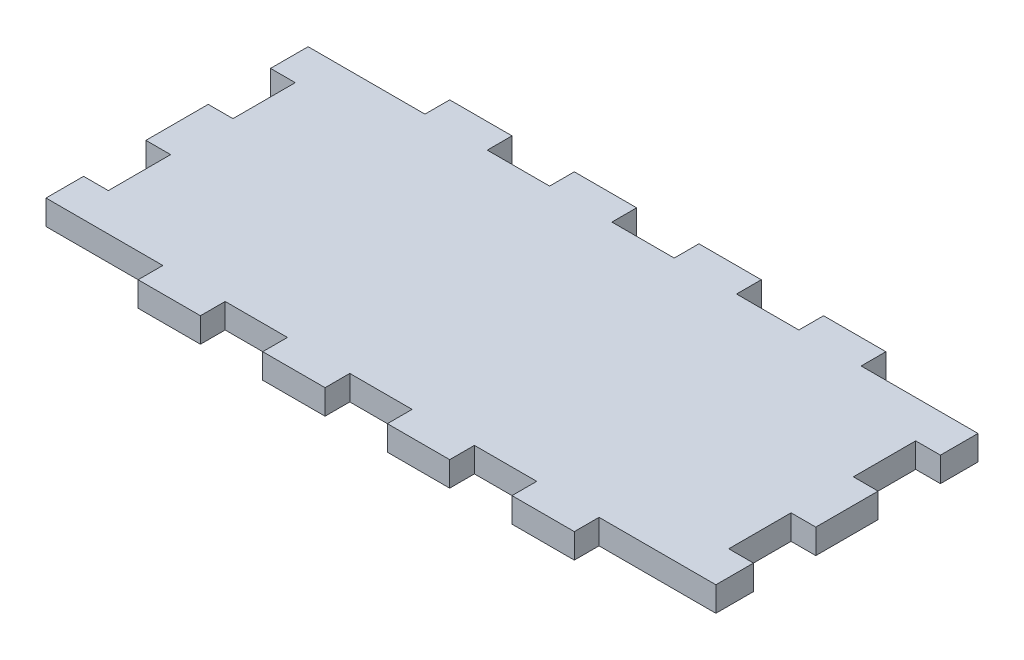
SolidWorks part; units mm, degrees
ref_plane "Front Plane" through (0, 0, 0) normal (0, 0, 1) x (1, 0, 0)
ref_plane "Top Plane" through (0, 0, 0) normal (0, 1, 0) x (1, 0, 0)
ref_plane "Right Plane" through (0, 0, 0) normal (1, 0, 0) x (0, 0, -1)
sketch "Sketch1" plane through (0, 0, 0) normal (0, 1, 0) x (1, 0, 0)
  line L1 (0, 0) -> (86, 0)
  line L2 (0, 0) -> (0, -40)
  line L3 (0, -40) -> (86, -40)
  line L4 (86, 0) -> (86, -40)
  dimension "D1" = 40
  dimension "D2" = 86
extrude "Boss-Extrude1" add sketch "Sketch1" along normal blind 3.175
sketch "Sketch2" plane through (0, 3.175, 0) normal (0, 1, 0) x (1, 0, 0)
  line L0 (43, 0) -> (43, -40) construction
  line L1 (86, 0) -> (0, 0) construction
  line L2 (0, -40) -> (86, -40) construction
  line L3 (0, -20) -> (86, -20) construction
  line L4 (0, 0) -> (0, -40) construction
  line L5 (86, -40) -> (86, 0) construction
  line L6 (15, 0) -> (15, -3.175)
  line L7 (39, 0) -> (47, 0)
  line L8 (0, -3.175) -> (15, -3.175)
  line L9 (39, -3.175) -> (47, -3.175)
  line L10 (47, 0) -> (47, -3.175)
  line L11 (55, 0) -> (63, 0)
  line L12 (55, 0) -> (55, -3.175)
  line L13 (55, -3.175) -> (63, -3.175)
  line L14 (63, 0) -> (63, -3.175)
  line L15 (86, 0) -> (71, 0)
  line L16 (86, 0) -> (86, -3.175)
  line L17 (86, -3.175) -> (71, -3.175)
  line L18 (71, 0) -> (71, -3.175)
  line L19 (0, 0) -> (0, -3.175)
  line L20 (0, 0) -> (15, 0)
  line L21 (23, 0) -> (23, -3.175)
  line L22 (31, -3.175) -> (23, -3.175)
  line L23 (31, 0) -> (31, -3.175)
  line L24 (31, 0) -> (23, 0)
  line L25 (39, 0) -> (39, -3.175)
  line L26 (39, -40) -> (39, -36.825)
  line L27 (31, -40) -> (23, -40)
  line L28 (31, -40) -> (31, -36.825)
  line L29 (31, -36.825) -> (23, -36.825)
  line L30 (23, -40) -> (23, -36.825)
  line L31 (0, -40) -> (15, -40)
  line L32 (0, -40) -> (0, -36.825)
  line L33 (71, -40) -> (71, -36.825)
  line L34 (86, -36.825) -> (71, -36.825)
  line L35 (86, -40) -> (86, -36.825)
  line L36 (86, -40) -> (71, -40)
  line L37 (63, -40) -> (63, -36.825)
  line L38 (55, -36.825) -> (63, -36.825)
  line L39 (55, -40) -> (55, -36.825)
  line L40 (55, -40) -> (63, -40)
  line L41 (47, -40) -> (47, -36.825)
  line L42 (39, -36.825) -> (47, -36.825)
  line L43 (0, -36.825) -> (15, -36.825)
  line L44 (39, -40) -> (47, -40)
  line L45 (15, -40) -> (15, -36.825)
  point P34 (43, -3.175)
  point P54 (43, -36.825)
  dimension "D1" = 4
  dimension "D2" = 3.175
  dimension "D3" = 3.175
  dimension "D4" = 8
  dimension "D5" = 8
  dimension "D6" = 3.175
  dimension "D7" = 8
extrude "Cut-Extrude1" cut sketch "Sketch2" against normal up to next
sketch "Sketch3" plane through (0, 3.175, 0) normal (0, 1, 0) x (1, 0, 0)
  line L0 (0, -20) -> (86, -20) construction
  line L1 (0, -3.175) -> (0, -36.825) construction
  line L2 (86, -36.825) -> (86, -3.175) construction
  line L3 (3.175, -24) -> (3.175, -32)
  line L4 (0, -16) -> (3.175, -16)
  line L5 (0, -16) -> (0, -8)
  line L6 (0, -8) -> (3.175, -8)
  line L7 (3.175, -16) -> (3.175, -8)
  line L8 (0, -32) -> (3.175, -32)
  line L9 (0, -24) -> (0, -32)
  line L10 (0, -24) -> (3.175, -24)
  line L11 (43, -3.175) -> (43, -36.825) construction
  line L12 (39, -3.175) -> (47, -3.175) construction
  line L13 (47, -36.825) -> (39, -36.825) construction
  line L14 (86, -24) -> (82.825, -24)
  line L15 (86, -24) -> (86, -32)
  line L16 (86, -32) -> (82.825, -32)
  line L17 (82.825, -16) -> (82.825, -8)
  line L18 (86, -8) -> (82.825, -8)
  line L19 (86, -16) -> (86, -8)
  line L20 (86, -16) -> (82.825, -16)
  line L21 (82.825, -24) -> (82.825, -32)
  dimension "D1" = 8
  dimension "D2" = 3.175
  dimension "D3" = 4
extrude "Cut-Extrude2" cut sketch "Sketch3" against normal up to next
